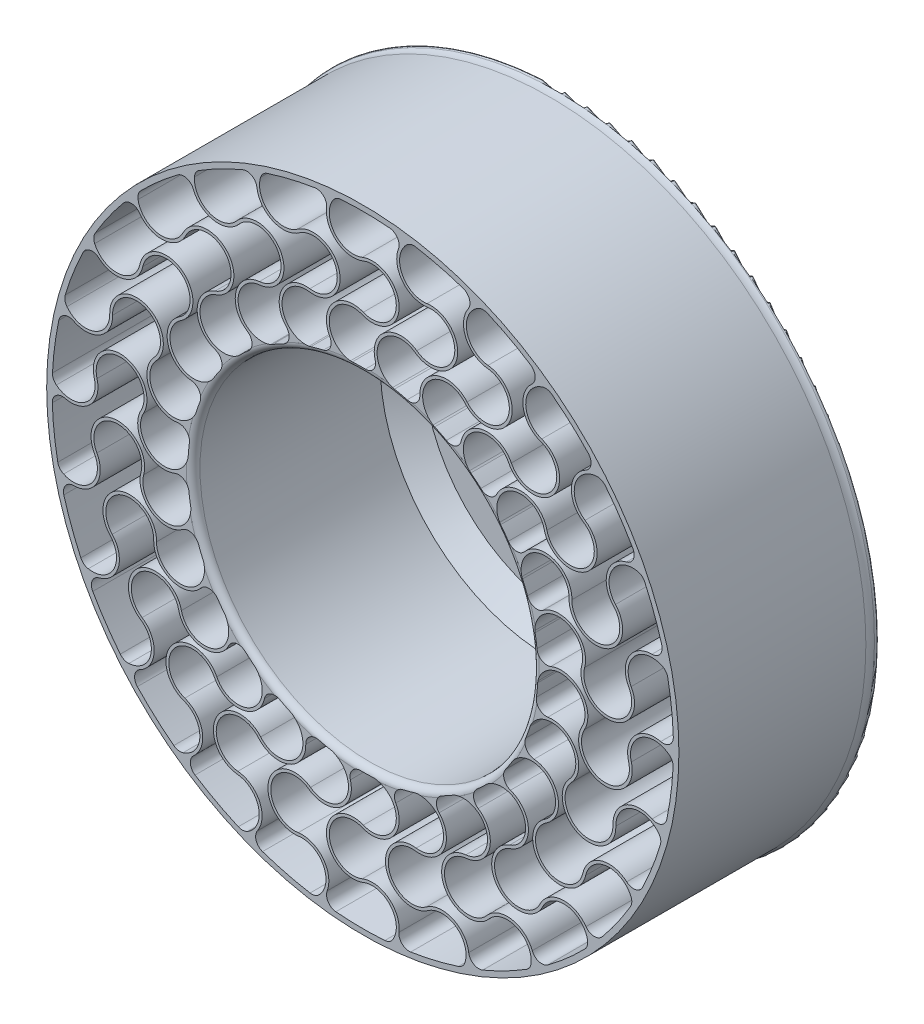
SolidWorks part; units mm, degrees
ref_plane "Front Plane" through (0, 0, 0) normal (0, 0, 1) x (1, 0, 0)
ref_plane "Top Plane" through (0, 0, 0) normal (0, 1, 0) x (1, 0, 0)
ref_plane "Right Plane" through (0, 0, 0) normal (1, 0, 0) x (0, 0, -1)
sketch "Sketch1" plane through (0, 0, 0) normal (0, 0, 1) x (1, 0, 0)
  circle A0 centre (0, 0) radius 24.95
  circle A1 centre (0, 0) radius 25.75
  dimension "D1" = 49.9
  dimension "D2" = 0.8
extrude "Boss-Extrude1" add sketch "Sketch1" along normal blind 27.5
sketch "Sketch2" plane through (0, 0, 27.5) normal (0, 0, 1) x (1, 0, 0)
  line L0 (0, 46.5) -> (0, 25.75) construction
  line L1 (0, 0) -> (0, -25.95) construction
  line L4 (0, 0) -> (0, 25.75) construction
  circle A0 centre (0, 0) radius 25.75 construction
  circle A1 centre (0, 0) radius 46.5 construction
  arc A2 (-3.5288, 46.3659) -> (-2.3332, 46.4414) centre (0, 0) cw
  arc A13 (0, 46.5) -> (0, 39.5833) centre (-1.4071, 43.0417) ccw construction
  arc A14 (0, 39.5833) -> (0, 32.6667) centre (1.4071, 36.125) cw construction
  arc A15 (0, 32.6667) -> (0, 25.75) centre (-1.4071, 29.2083) ccw construction
  arc A16 (-2.3332, 46.4414) -> (-0.0791, 39.7778) centre (-1.4071, 43.0417) ccw
  arc A17 (-0.0791, 39.7778) -> (-0.0791, 32.4722) centre (1.4071, 36.125) cw
  arc A18 (-0.0791, 32.4722) -> (-1.679, 25.6952) centre (-1.4071, 29.2083) ccw
  arc A19 (-3.5288, 46.3659) -> (0.0791, 39.3888) centre (-1.4071, 43.0417) ccw
  arc A20 (0.0791, 39.3888) -> (0.0791, 32.8612) centre (1.4071, 36.125) cw
  arc A21 (0.0791, 32.8612) -> (-2.9526, 25.5802) centre (-1.4071, 29.2083) ccw
  arc A22 (-0.0791, 46.3055) -> (-0.0791, 39.7778) centre (-1.4071, 43.0417) ccw construction
  arc A23 (0.0791, 46.6945) -> (0.0791, 39.3888) centre (-1.4071, 43.0417) ccw construction
  arc A24 (-0.0791, 32.4722) -> (-0.0791, 25.9445) centre (-1.4071, 29.2083) ccw construction
  arc A25 (0.0791, 32.8612) -> (0.0791, 25.5555) centre (-1.4071, 29.2083) ccw construction
  circle A26 centre (0, 0) radius 25.75 construction
  arc A27 (0, 46.5) -> (0, 39.5833) centre (-1.4071, 43.0417) ccw construction
  arc A28 (0, 39.5833) -> (0, 32.6667) centre (1.4071, 36.125) cw construction
  arc A29 (-2.9526, 25.5802) -> (-1.679, 25.6952) centre (0, 0) cw
  arc A30 (0, 32.6667) -> (0, 25.75) centre (-1.4071, 29.2083) ccw construction
  arc A31 (-0.0791, 39.7778) -> (-0.0791, 32.4722) centre (1.4071, 36.125) cw construction
  point P3 (-1.4071, 43.0417)
  dimension "D1" = 93
  dimension "D6" = 0.21
  dimension "D5" = 0.21
extrude "SupportElement" add sketch "Sketch2" against normal through all
sketch "Sketch3" plane through (0, 0, 27.5) normal (0, 0, 1) x (1, 0, 0)
  circle A0 centre (0, 0) radius 46.5
  circle A1 centre (0, 0) radius 45.7
  arc A2 (-2.3332, 46.4414) -> (-3.5288, 46.3659) centre (0, 0) ccw construction
  dimension "D1" = 0.8
extrude "WheelRim" add sketch "Sketch3" against normal through all
fillet "SupportFillet" radius 1.5 4 edges at (-4.5089, 45.477, 13.75) (-2.9526, 25.5802, 13.75) (-1.679, 25.6952, 13.75) (-3.8985, 45.5334, 13.75)
pattern_circular "CirPattern1" count 26 over 360 about axis through (0, 0, 27.5) along (0, 0, -1) of "SupportFillet", "SupportElement"
sketch "Sketch5" plane through (0, 0, 0) normal (0, 1, 0) x (1, 0, 0)
  line L0 (0, 0) -> (0, 31.5884) construction
  line L1 (-24.95, 0) -> (-21.75, 3.1932)
  line L2 (-21.75, 3.1932) -> (0, 3.1932)
  line L3 (0, 3.1932) -> (0, 3.9932)
  line L4 (0, 3.9932) -> (-21.75, 3.9932)
  line L5 (-21.75, 3.9932) -> (-25.75, 0)
  line L6 (-25.75, 0) -> (-24.95, 0)
  line L7 (46.5, 0) -> (-46.5, 0) construction
  line L8 (-21.75, 3.9932) -> (-21.75, 3.1932) construction
  line L9 (46.5, 0) -> (-46.5, 0) construction
  line L11 (-46.5, 0) -> (-45.7, 0)
  arc A0 (-46.5, 0) -> (-46.7679, 1) centre (-48.5, 0) ccw
  arc A1 (-45.7, 0) -> (-46.0751, 1.4) centre (-48.5, 0) ccw
  arc A2 (-46.7679, 1) -> (-46.0751, 1.4) centre (-46.4215, 1.2) cw
  dimension "D3" = 0.8
  dimension "D4" = 2
  dimension "D1" = 51.5
  dimension "D2" = 0.8
  dimension "D5" = 1
  dimension "D6" = 0.8
revolve "Revolve1" add sketch "Sketch5" angle 360 about L0
sketch "Sketch6" plane through (0, 0, -3.1932) normal (0, 0, 1) x (1, 0, 0)
  circle A0 centre (-17, 0) radius 3.5 construction
  circle A1 centre (0, 17) radius 3.5 construction
  circle A2 centre (0, -17) radius 3.5 construction
  circle A3 centre (17, 0) radius 3.5 construction
  circle A4 centre (-17, 0) radius 3.5 construction
  circle A5 centre (0, 17) radius 3.5 construction
  circle A6 centre (0, -17) radius 3.5 construction
  circle A7 centre (17, 0) radius 3.5 construction
  circle A8 centre (-17, 0) radius 3.35
  circle A9 centre (0, -17) radius 3.35
  circle A10 centre (17, 0) radius 3.35
  circle A11 centre (0, 17) radius 3.35
  dimension "D1" = 6.7
extrude "Boss-Extrude2" add sketch "Sketch6" along normal blind 3
sketch "Sketch7" plane through (0, 0, -0.1932) normal (0, 0, 1) x (1, 0, 0)
  circle A0 centre (0, -17) radius 3.35 construction
  circle A1 centre (17, 0) radius 3.35 construction
  circle A2 centre (0, 17) radius 3.35 construction
  circle A3 centre (-17, 0) radius 3.35 construction
  circle A4 centre (0, -17) radius 3.35 construction
  circle A5 centre (17, 0) radius 3.35 construction
  circle A6 centre (0, 17) radius 3.35 construction
  circle A7 centre (-17, 0) radius 3.35 construction
  circle A8 centre (-17, 0) radius 1.45
  circle A9 centre (0, 17) radius 1.45
  circle A10 centre (17, 0) radius 1.45
  circle A11 centre (0, -17) radius 1.45
  dimension "D1" = 2.9
extrude "Cut-Extrude1" cut sketch "Sketch7" against normal through all
fillet "Fillet2" radius 1 5 edges at (24.95, 0, 27.5) (-13.65, 0, -0.1932) (3.35, -17, -0.1932) (3.35, 17, -0.1932) (20.35, 0, -0.1932)
ref_plane "Plane1" through (0, 0, 13.75) normal (0, 0, 1) x (1, 0, 0)
sketch "Sketch8" plane through (0, 0, 0) normal (0, 1, 0) x (1, 0, 0)
  line L1 (108.8481, 29.3599) -> (-95.1042, 29.3599)
  line L2 (108.8481, 29.3599) -> (108.8481, 0)
  line L3 (108.8481, 0) -> (-95.1042, 0)
  line L4 (-95.1042, 29.3599) -> (-95.1042, 0)
  line L5 (46.5, 0) -> (-46.5, 0) construction
extrude "Cut-Extrude2" [suppressed] cut sketch "Sketch8" against normal through all and the other way through all
fillet "Fillet3" [suppressed] radius 10
